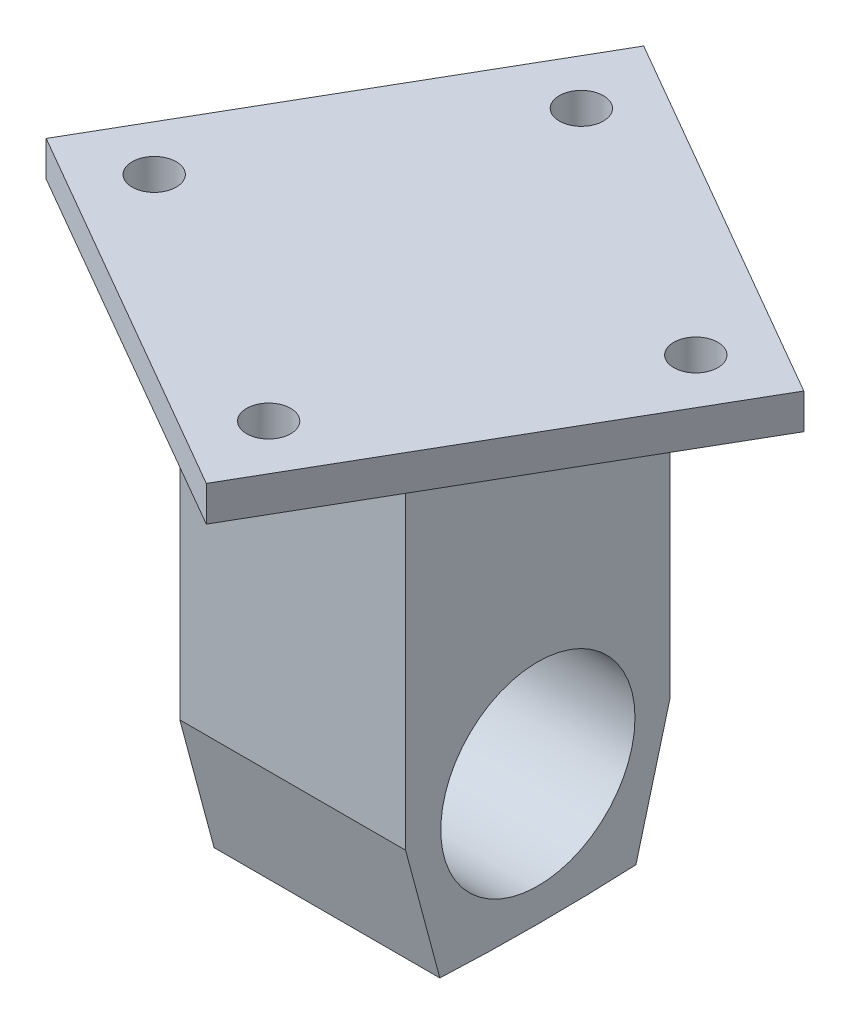
SolidWorks part; units mm, degrees
material "ABS"
ref_plane "Front Plane" through (0, 0, 0) normal (0, 0, 1) x (1, 0, 0)
ref_plane "Top Plane" through (0, 0, 0) normal (0, 1, 0) x (1, 0, 0)
ref_plane "Right Plane" through (0, 0, 0) normal (1, 0, 0) x (0, 0, -1)
sketch "Sketch1" plane through (0, 0, 0) normal (0, 1, 0) x (1, 0, 0)
  line L1 (-16.256, -19.05) -> (16.256, -19.05)
  line L2 (-16.256, -19.05) -> (-16.256, 19.05)
  line L3 (-16.256, 19.05) -> (16.256, 19.05)
  line L4 (16.256, -19.05) -> (16.256, 19.05)
  line L5 (-16.256, -19.05) -> (16.256, 19.05) construction
  line L6 (-16.256, 19.05) -> (16.256, -19.05) construction
  point P0 (0, 0)
extrude "Boss-Extrude1" add sketch "Sketch1" along normal blind 50.292
sketch "Sketch2" plane through (16.256, 0, 0) normal (1, 0, 0) x (0, 0, -1)
  line L0 (-19.05, 0) -> (-14.1195, -18.4009)
  line L1 (19.05, 0) -> (14.1195, -18.4009)
  line L2 (-19.05, 0) -> (19.05, 0)
  line L3 (-19.05, 0) -> (19.05, 0) construction
  arc A1 (14.1195, -18.4009) -> (-14.1195, -18.4009) centre (0, 281.2546) cw
  dimension "D1" = 19.05
  dimension "D2" = 19.05
  dimension "D3" = 75
  dimension "D4" = 75
extrude "Boss-Extrude2" add sketch "Sketch2" against normal up to vertex (32.512 mm away) contours L0 A1 L1 L2 up to point (-16.256, 0, -19.05)
sketch "Sketch3" plane through (16.256, 0, 0) normal (1, 0, 0) x (0, 0, -1)
  circle A0 centre (0, 0) radius 13.9872
extrude "Cut-Extrude1" cut sketch "Sketch3" against normal blind 127 contours A0
sketch "Sketch4" plane through (0, 50.292, 0) normal (0, 1, 0) x (1, 0, 0)
  line L0 (-46.8473, -12.5527) -> (46.8473, 12.5527) construction
  line L5 (13.6389, -50.901) -> (-13.6389, 50.901) construction
  line L6 (43.0243, 11.5283) -> (11.5283, -43.0243)
  line L11 (11.5283, -43.0243) -> (-43.0243, -11.5283)
  line L12 (-43.0243, -11.5283) -> (-11.5283, 43.0243)
  line L13 (-11.5283, 43.0243) -> (43.0243, 11.5283)
  line L14 (11.5283, -43.0243) -> (-11.5283, 43.0243) construction
  line L15 (-43.0243, -11.5283) -> (43.0243, 11.5283) construction
  point P1 (0, 0)
  point P4 (0, 0)
  point P11 (0, 0)
  dimension "D1" = 62.992
  dimension "D2" = 62.992
  dimension "D3" = 0
  dimension "D4" = 0
extrude "Boss-Extrude3" add sketch "Sketch4" along normal blind 5.08
sketch "Sketch5" plane through (0, 55.372, 0) normal (0, 1, 0) x (1, 0, 0)
  line L2 (30.7571, 8.2413) -> (43.0243, 11.5283) construction
  line L3 (8.2413, -30.7571) -> (11.5283, -43.0243) construction
  line L4 (-30.7571, -8.2413) -> (-43.0243, -11.5283) construction
  line L5 (-8.2413, 30.7571) -> (-11.5283, 43.0243) construction
  line L6 (-11.5283, 43.0243) -> (-43.0243, -11.5283) construction
  line L7 (43.0243, 11.5283) -> (-11.5283, 43.0243) construction
  line L8 (-43.0243, -11.5283) -> (11.5283, -43.0243) construction
  circle A0 centre (30.7571, 8.2413) radius 3.175
  circle A1 centre (8.2413, -30.7571) radius 3.175
  circle A2 centre (-8.2413, 30.7571) radius 3.175
  circle A3 centre (-30.7571, -8.2413) radius 3.175
  dimension "D2" = 6.35
  dimension "D4" = 6.35
  dimension "D11" = 6.35
  dimension "D12" = 6.35
  dimension "D1" = 12.7
  dimension "D3" = 45
  dimension "D5" = 12.7
  dimension "D6" = 45
  dimension "D7" = 12.7
  dimension "D8" = 45
  dimension "D9" = 12.7
  dimension "D10" = 45
extrude "Cut-Extrude2" cut sketch "Sketch5" against normal through all
